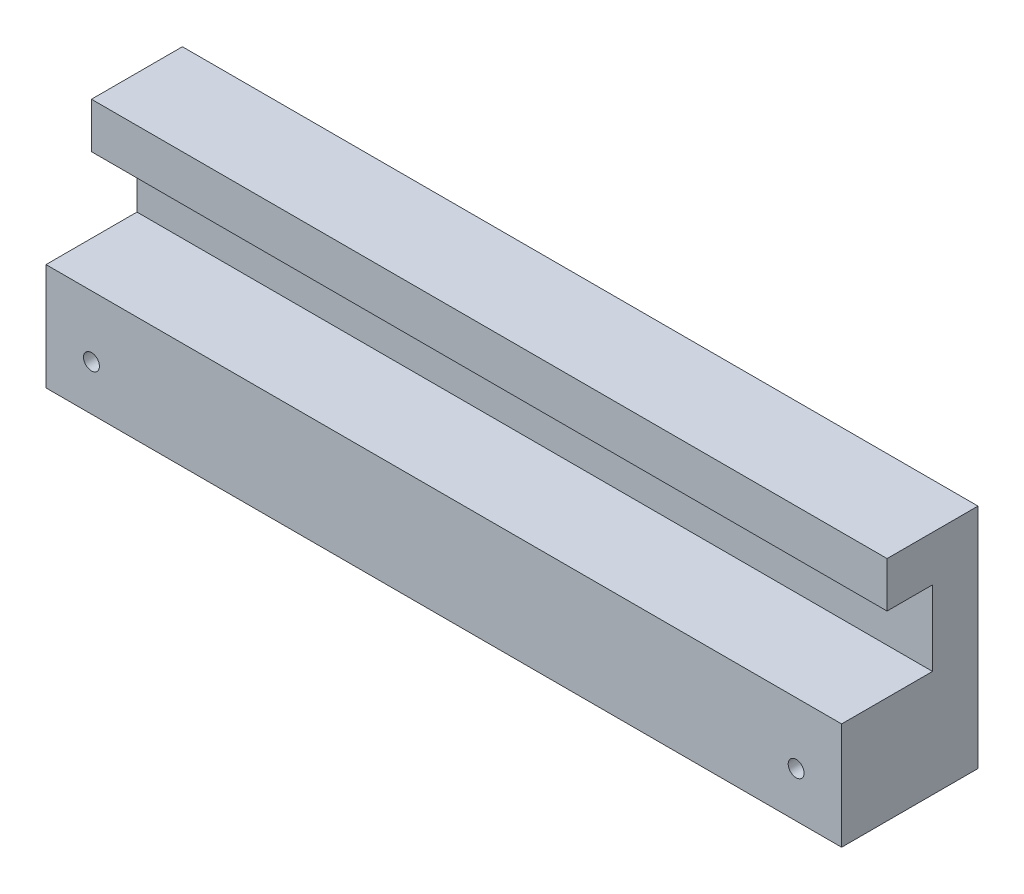
SolidWorks part; units mm, degrees
ref_plane "前视基准面" through (0, 0, 0) normal (0, 0, 1) x (1, 0, 0)
ref_plane "上视基准面" through (0, 0, 0) normal (0, 1, 0) x (1, 0, 0)
ref_plane "右视基准面" through (0, 0, 0) normal (1, 0, 0) x (0, 0, -1)
other "Configuration Table"
sketch "草图1" plane through (0, 0, 0) normal (0, 0, 1) x (1, 0, 0)
  line L9 (-17.5, 5) -> (17.5, 5)
  line L10 (-17.5, 5) -> (-17.5, -5)
  line L11 (-17.5, -5) -> (17.5, -5)
  line L12 (17.5, 5) -> (17.5, -5)
  line L13 (-17.5, 5) -> (-19.5, 5)
  line L14 (-17.5, 5) -> (-17.5, -5)
  line L15 (-17.5, -5) -> (-19.5, -5)
  line L16 (-19.5, 5) -> (-19.5, -5)
  line L17 (17.5, -5) -> (19.5, -5)
  line L18 (17.5, -5) -> (17.5, 5)
  line L19 (17.5, 5) -> (19.5, 5)
  line L20 (19.5, -5) -> (19.5, 5)
  line L21 (-19.5, 5) -> (-22.5, 5)
  line L42 (-19.5, 5) -> (-19.5, 2)
  line L43 (-19.5, 2) -> (-22.5, 2)
  line L44 (-22.5, 5) -> (-22.5, 2)
  line L45 (-19.5, -5) -> (-22.5, -5)
  line L46 (-19.5, -5) -> (-19.5, -2)
  line L47 (-19.5, -2) -> (-22.5, -2)
  line L48 (-22.5, -5) -> (-22.5, -2)
  line L49 (19.5, -5) -> (22.5, -5)
  line L50 (19.5, -5) -> (19.5, -2)
  line L51 (19.5, -2) -> (22.5, -2)
  line L52 (22.5, -5) -> (22.5, -2)
  line L53 (19.5, 5) -> (22.5, 5)
  line L54 (19.5, 5) -> (19.5, 2)
  line L55 (19.5, 2) -> (22.5, 2)
  line L56 (22.5, 5) -> (22.5, 2)
  circle A12 centre (-21, 3.5) radius 0.6
  circle A13 centre (-21, -3.5) radius 0.6
  circle A14 centre (21, -3.5) radius 0.6
  circle A15 centre (21, 3.5) radius 0.6
  point P4 (0, 5)
  point P6 (-17.5, 0)
  point P32 (-21, 5)
  point P33 (-22.5, 3.5)
  point P35 (22.5, -3.5)
  point P37 (21, -5)
  dimension "D4" = 3
  dimension "D1" = 10
  dimension "D2" = 35
  dimension "D3" = 2
  dimension "D6" = 1.2
  dimension "D5" = 3
extrude "凸台-拉伸1" add sketch "草图1" along normal blind 2 contours L11 L12 L9 L10
sketch "草图3" plane through (0, 0, 2) normal (0, 0, 1) x (1, 0, 0)
  line L1 (-17.5, 5) -> (17.5, 5)
  line L2 (-17.5, 5) -> (-17.5, 3)
  line L3 (-17.5, 3) -> (17.5, 3)
  line L4 (17.5, 5) -> (17.5, 3)
  line L5 (17.5, 5) -> (17.5, -5) construction
  line L7 (-17.5, -5) -> (17.5, -5)
  line L8 (-17.5, -5) -> (-17.5, -0.3)
  line L9 (-17.5, -0.3) -> (17.5, -0.3)
  line L10 (17.5, -5) -> (17.5, -0.3)
  dimension "D1" = 2
  dimension "D2" = 3.3
extrude "凸台-拉伸2" add sketch "草图3" along normal blind 2 contours L3 L4 L1 L2
extrude "凸台-拉伸3" add sketch "草图3<3>" along normal blind 4 contours L7 L10 L9 L8
sketch "草图3<3>" plane through (0, 0, 2) normal (0, 0, 1) x (1, 0, 0) same geometry as "草图3"
sketch "草图4" plane through (0, 0, 6) normal (0, 0, 1) x (1, 0, 0)
  line L0 (-17.5, -5) -> (17.5, -5) construction
  line L1 (-17.5, -5) -> (-17.5, -0.3) construction
  line L2 (17.5, -5) -> (17.5, -0.3) construction
  circle A0 centre (15.5, -3) radius 0.35
  circle A1 centre (-15.5, -3) radius 0.35
  point P8 (0, 0)
  dimension "D2" = 0.7
  dimension "D1" = 2
  dimension "D3" = 2
  dimension "D4" = 2
extrude "切除-拉伸1" cut sketch "草图4" against normal through all
